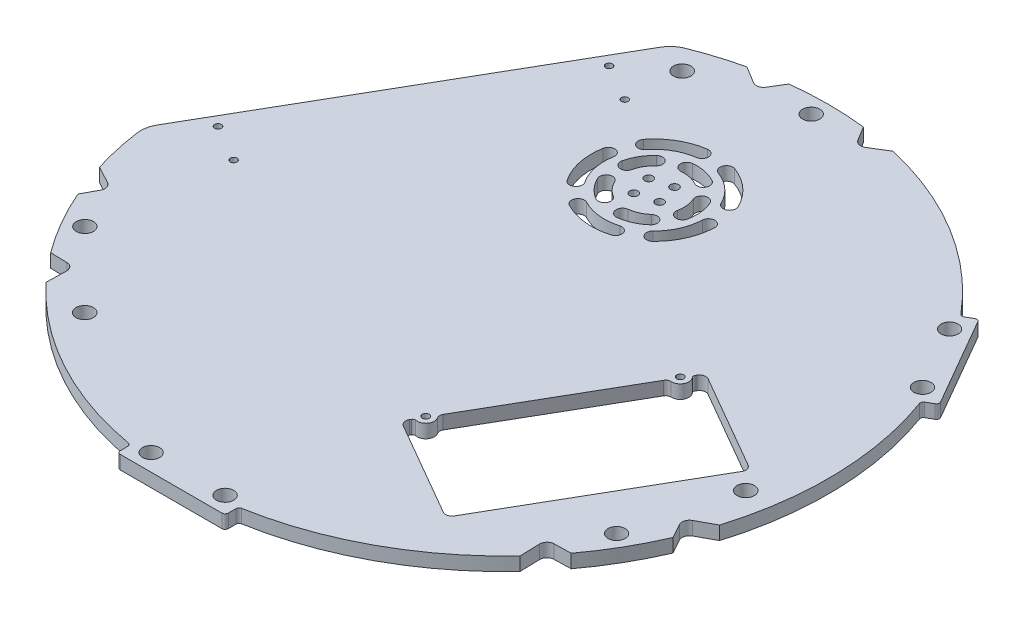
SolidWorks part; units mm, degrees
ref_plane "Front Plane" through (0, 0, 0) normal (0, 0, 1) x (1, 0, 0)
ref_plane "Top Plane" through (0, 0, 0) normal (0, 1, 0) x (1, 0, 0)
ref_plane "Right Plane" through (0, 0, 0) normal (1, 0, 0) x (0, 0, -1)
sketch "Sketch1" plane through (0, 0, 0) normal (0, 1, 0) x (1, 0, 0)
  circle A0 centre (0, 0) radius 152.4
  dimension "D1" = 304.8
extrude "Boss-Extrude1" add sketch "Sketch1" along normal blind 6.35
sketch "Sketch2" plane through (0, 6.35, 0) normal (0, 1, 0) x (1, 0, 0)
  line L0 (0, 144.3376) -> (0, 0) construction
  line L1 (0, 0) -> (0, 144.3376) construction
  line L2 (0, 0) -> (125, -72.1688) construction
  circle A0 centre (0, 144.3376) radius 4.05
  circle A2 centre (125, -72.1688) radius 4.05
  circle A3 centre (-125, -72.1688) radius 4.05
  point P11 (0, 0)
  dimension "D1" = 8.1
  dimension "D2" = 144.3376
  dimension "D4" = 144.3376
  dimension "D5" = 120
  dimension "D3" = 3
extrude "Cut-Extrude1" cut sketch "Sketch2" against normal through all
sketch "Sketch3" plane through (0, 6.35, 0) normal (0, 1, 0) x (1, 0, 0)
  line L0 (0, -150.2684) -> (0, 0) construction
  line L1 (-25.4, -150.2684) -> (25.4, -150.2684)
  line L2 (-25.4, -150.2684) -> (-25.4, -156.6184)
  line L3 (-25.4, -156.6184) -> (25.4, -156.6184)
  line L4 (25.4, -150.2684) -> (25.4, -156.6184)
  dimension "D1" = 50.8
  dimension "D2" = 6.35
extrude "Boss-Extrude2" add sketch "Sketch3" against normal blind 6.35
sketch "Sketch4" plane through (0, 6.35, 0) normal (0, 1, 0) x (1, 0, 0)
  line L2 (-17.4, -148.6184) -> (17.4, -148.6184) construction
  line L3 (0, -148.6184) -> (0, -156.6184) construction
  circle A0 centre (17.4, -148.6184) radius 4.05
  circle A1 centre (-17.4, -148.6184) radius 4.05
extrude "Cut-Extrude2" cut sketch "Sketch4" against normal through all
fillet "Fillet1" radius 1.5 4 edges at (-25.4, 3.175, 150.2684) (-25.4, 3.175, 156.6184) (25.4, 3.175, 150.2684) (25.4, 3.175, 156.6184)
sketch "Sketch5" plane through (0, 0, 0) normal (0, -1, 0) x (1, 0, 0)
  line L0 (-39.9277, -175.6648) -> (-166.1966, 43.0393)
  line L17 (-70.2484, -123.1479) -> (-141.7734, 0.7371) construction
extrude "Cut-Extrude3" cut sketch "Sketch5" against normal through all and the other way through all
sketch "Sketch6" [suppressed] plane through (0, 0, 0) normal (0, -1, 0) x (1, 0, 0)
  line L0 (-173.1347, -15.6374) -> (-100.1097, -142.1204)
  line L1 (-100.1097, -142.1204) -> (-79.3315, -130.1241)
  line L3 (-79.3315, -130.1241) -> (-152.3565, -3.6411)
  line L4 (-152.3565, -3.6411) -> (-173.1347, -15.6374)
  arc A2 (-26.6378, 150.0539) -> (26.6378, 150.0539) centre (0, 0) ccw construction
extrude "Boss-Extrude3" [suppressed] add sketch "Sketch6" against normal blind 6.35
fillet "Fillet2" [suppressed] radius 1.5
sketch "Sketch7" plane through (0, 6.35, 0) normal (0, 1, 0) x (1, 0, 0)
  circle A1 centre (-89.9903, -107.2462) radius 4.1
  circle A3 centre (-47.8828, 131.557) radius 4.1
  circle A5 centre (137.8731, -24.3107) radius 4.1
extrude "Cut-Extrude4" cut sketch "Sketch7" against normal through all
sketch "Sketch8" plane through (0, 0, 0) normal (0, -1, 0) x (1, 0, 0)
  circle A0 centre (-89.9903, 107.2462) radius 15
  circle A1 centre (-89.9903, 107.2462) radius 4.1 construction
  circle A2 centre (-47.8828, -131.557) radius 15
  circle A4 centre (137.8731, 24.3107) radius 15
  circle A5 centre (137.8731, 24.3107) radius 4.1 construction
  dimension "D1" = 30
sketch "Sketch9" plane through (0, 0, 0) normal (0, 1, 0) x (1, 0, 0)
  line L0 (-114.4897, -91.0492) -> (-125.4859, -90.7618)
  line L1 (-111.1769, -94.6245) -> (-111.8439, -120.1454)
  line L3 (0, 0) -> (-125, -72.1688) construction
  line L6 (-136.0957, -53.6264) -> (-141.345, -63.2931)
  line L7 (-137.5356, -48.9698) -> (-159.9709, -36.7869)
  arc A1 (-141.345, -63.2931) -> (-125.4859, -90.7618) centre (-125, -72.1688) ccw
  arc A2 (-159.9709, -36.7869) -> (-111.8439, -120.1454) centre (-125, -72.1688) ccw
  spline S0 degree 3 poles (-114.4897, -91.0492) (-114.0345, -91.0611) (-113.1163, -91.2801) (-111.6342, -92.3884) (-111.1542, -93.7538) (-111.1769, -94.6245) knots 0 0 0 0 0.392699 0.785398 1.570796 1.570796 1.570796 1.570796
  spline S1 degree 3 poles (-136.0957, -53.6264) (-135.8785, -53.2263) (-135.609, -52.3215) (-135.8277, -50.4838) (-136.7702, -49.3854) (-137.5356, -48.9698) knots 0 0 0 0 0.392699 0.785398 1.570796 1.570796 1.570796 1.570796
  dimension "D1" = 49.7477
extrude "Cut-Extrude5" cut sketch "Sketch9" along normal through all
pattern_circular "CirPattern1" count 3 every 120 about axis through (0, 6.35, 0) along (0, -1, 0) of "Cut-Extrude5"
sketch "Sketch10" plane through (0, 6.35, 0) normal (0, 1, 0) x (1, 0, 0)
  line L4 (-19.0051, -114.3124) -> (14.6313, -133.7324)
  line L5 (32.2903, -17.8461) -> (-20.3997, -109.1078)
  line L6 (71.1313, -35.8715) -> (37.4949, -16.4515)
  line L7 (19.8359, -132.3378) -> (72.5259, -41.0761)
  arc A4 (-20.3997, -109.1078) -> (-19.0051, -114.3124) centre (-17.1001, -111.0128) ccw
  arc A5 (37.4949, -16.4515) -> (32.2903, -17.8461) centre (35.5899, -19.7511) ccw
  arc A6 (72.5259, -41.0761) -> (71.1313, -35.8715) centre (69.2263, -39.1711) ccw
  arc A7 (14.6313, -133.7324) -> (19.8359, -132.3378) centre (16.5363, -130.4328) ccw
extrude "Cut-Extrude6" cut sketch "Sketch10" against normal through all
sketch "Sketch12" [suppressed] plane through (0, 0, 0) normal (0, -1, 0) x (1, 0, 0)
  circle A5 centre (-100.754, 34.2057) radius 1.525
  circle A6 centre (-12.004, -119.5138) radius 1.525
  circle A7 centre (70.2684, -72.0138) radius 1.525
  circle A8 centre (-8.599, -16.5116) radius 1.525
  circle A9 centre (-18.4816, 81.7057) radius 1.525
extrude "Cut-Extrude7" [suppressed] cut sketch "Sketch12" against normal blind 25.4
fillet "Fillet4" radius 12.7 2 edges at (-60.6199, 3.175, -139.8248) (-151.4018, 3.175, 17.414)
ref_plane "Plane1" through (0, 0, 0) normal (0.5, 0, -0.866) x (-0.866, 0, -0.5)
mirror "Mirror1" about plane through (0, 0, 0) normal (0.5, 0, -0.866) of "Cut-Extrude2", "Fillet1", "Boss-Extrude2"
sketch "Sketch13" plane through (0, 6.35, 0) normal (0, 1, 0) x (1, 0, 0)
  line L0 (-67.1597, 116.4976) -> (-46.3248, 104.4685) construction
  line L3 (-134.4697, -0.0868) -> (-113.6348, -12.1158) construction
  line L5 (-117.0989, -10.1158) -> (-49.7889, 106.4685) construction
  circle A0 centre (-134.4697, -0.0868) radius 1.6
  circle A1 centre (-117.0989, -10.1158) radius 1.6
  circle A2 centre (-67.1597, 116.4976) radius 1.6
  circle A3 centre (-49.7889, 106.4685) radius 1.6
extrude "Cut-Extrude8" cut sketch "Sketch13" against normal blind 25.4
sketch "Sketch14" [suppressed] plane through (0, 0, 0) normal (0, -1, 0) x (1, 0, 0)
  line L0 (-5.7127, 73.4893) -> (-38.7083, 54.4393) construction
  line L2 (-4.1252, 70.7397) -> (-37.1208, 51.6897)
  line L3 (-7.3002, 76.239) -> (-40.2958, 57.189)
  line L5 (-52.8678, 46.2643) -> (-33.982, 13.5531) construction
  line L6 (-100.0229, 19.0393) -> (-67.0273, 38.0893) construction
  line L7 (-98.4354, 16.2897) -> (-65.4398, 35.3397)
  line L8 (-101.6104, 21.789) -> (-68.6148, 40.839)
  line L9 (3.8123, 56.9915) -> (-29.1833, 37.9415) construction
  line L10 (5.3998, 54.2419) -> (-27.5958, 35.1919)
  line L11 (2.2248, 59.7412) -> (-30.7708, 40.6912)
  line L12 (-90.4979, 2.5415) -> (-57.5023, 21.5915) construction
  line L13 (-88.9104, -0.2081) -> (-55.9148, 18.8419)
  line L14 (-92.0854, 5.2912) -> (-59.0898, 24.3412)
  line L15 (13.3373, 40.4938) -> (-19.6583, 21.4438) construction
  line L16 (14.9248, 37.7441) -> (-18.0708, 18.6941)
  line L17 (11.7498, 43.2434) -> (-21.2458, 24.1934)
  line L18 (-80.9729, -13.9562) -> (-47.9773, 5.0938) construction
  line L19 (-79.3854, -16.7059) -> (-46.3898, 2.3441)
  line L20 (-82.5604, -11.2066) -> (-49.5648, 7.8434)
  line L21 (22.8623, 23.996) -> (-10.1333, 4.946) construction
  line L22 (24.4498, 21.2463) -> (-8.5458, 2.1963)
  line L23 (21.2748, 26.7456) -> (-11.7208, 7.6956)
  line L24 (-71.4479, -30.454) -> (-38.4523, -11.404) construction
  line L25 (-69.8604, -33.2037) -> (-36.8648, -14.1537)
  line L26 (-73.0354, -27.7044) -> (-40.0398, -8.6544)
  line L27 (32.3873, 7.4982) -> (-0.6083, -11.5518) construction
  line L28 (33.9748, 4.7486) -> (0.9792, -14.3014)
  line L29 (30.7998, 10.2478) -> (-2.1958, -8.8022)
  line L30 (-61.9229, -46.9518) -> (-28.9273, -27.9018) construction
  line L31 (-60.3354, -49.7014) -> (-27.3398, -30.6514)
  line L32 (-63.5104, -44.2022) -> (-30.5148, -25.1522)
  line L33 (41.9123, -8.9996) -> (8.9167, -28.0496) construction
  line L34 (43.4998, -11.7492) -> (10.5042, -30.7992)
  line L35 (40.3248, -6.25) -> (7.3292, -25.3)
  line L36 (-52.3979, -63.4496) -> (-19.4023, -44.3996) construction
  line L37 (-50.8104, -66.1992) -> (-17.8148, -47.1492)
  line L38 (-53.9854, -60.7) -> (-20.9898, -41.65)
  line L39 (51.4373, -25.4974) -> (18.4417, -44.5474) construction
  line L40 (53.0248, -28.247) -> (20.0292, -47.297)
  line L41 (49.8498, -22.7477) -> (16.8542, -41.7977)
  line L42 (-42.8729, -79.9474) -> (-9.8773, -60.8974) construction
  line L43 (-41.2854, -82.697) -> (-8.2898, -63.647)
  line L44 (-44.4604, -77.1977) -> (-11.4648, -58.1477)
  line L45 (60.9623, -41.9952) -> (27.9667, -61.0452) construction
  line L46 (62.5498, -44.7448) -> (29.5542, -63.7948)
  line L47 (59.3748, -39.2455) -> (26.3792, -58.2955)
  line L48 (-33.3479, -96.4452) -> (-0.3523, -77.3952) construction
  line L49 (-31.7604, -99.1948) -> (1.2352, -80.1448)
  line L50 (-34.9354, -93.6955) -> (-1.9398, -74.6455)
  line L51 (70.4873, -58.4929) -> (37.4917, -77.5429) construction
  line L52 (72.0748, -61.2426) -> (39.0792, -80.2926)
  line L53 (68.8998, -55.7433) -> (35.9042, -74.7933)
  line L54 (-23.8229, -112.9429) -> (9.1727, -93.8929) construction
  line L55 (-22.2354, -115.6926) -> (10.7602, -96.6426)
  line L56 (-25.4104, -110.1933) -> (7.5852, -91.1433)
  arc A0 (-4.1252, 70.7397) -> (-7.3002, 76.239) centre (-5.7127, 73.4893) ccw
  arc A1 (-40.2958, 57.189) -> (-37.1208, 51.6897) centre (-38.7083, 54.4393) ccw
  arc A2 (-98.4354, 16.2897) -> (-101.6104, 21.789) centre (-100.0229, 19.0393) cw
  arc A3 (-68.6148, 40.839) -> (-65.4398, 35.3397) centre (-67.0273, 38.0893) cw
  arc A4 (5.3998, 54.2419) -> (2.2248, 59.7412) centre (3.8123, 56.9915) ccw
  arc A5 (-30.7708, 40.6912) -> (-27.5958, 35.1919) centre (-29.1833, 37.9415) ccw
  arc A6 (-88.9104, -0.2081) -> (-92.0854, 5.2912) centre (-90.4979, 2.5415) cw
  arc A7 (-59.0898, 24.3412) -> (-55.9148, 18.8419) centre (-57.5023, 21.5915) cw
  arc A8 (14.9248, 37.7441) -> (11.7498, 43.2434) centre (13.3373, 40.4938) ccw
  arc A9 (-21.2458, 24.1934) -> (-18.0708, 18.6941) centre (-19.6583, 21.4438) ccw
  arc A10 (-79.3854, -16.7059) -> (-82.5604, -11.2066) centre (-80.9729, -13.9562) cw
  arc A11 (-49.5648, 7.8434) -> (-46.3898, 2.3441) centre (-47.9773, 5.0938) cw
  arc A12 (24.4498, 21.2463) -> (21.2748, 26.7456) centre (22.8623, 23.996) ccw
  arc A13 (-11.7208, 7.6956) -> (-8.5458, 2.1963) centre (-10.1333, 4.946) ccw
  arc A14 (-69.8604, -33.2037) -> (-73.0354, -27.7044) centre (-71.4479, -30.454) cw
  arc A15 (-40.0398, -8.6544) -> (-36.8648, -14.1537) centre (-38.4523, -11.404) cw
  arc A16 (33.9748, 4.7486) -> (30.7998, 10.2478) centre (32.3873, 7.4982) ccw
  arc A17 (-2.1958, -8.8022) -> (0.9792, -14.3014) centre (-0.6083, -11.5518) ccw
  arc A18 (-60.3354, -49.7014) -> (-63.5104, -44.2022) centre (-61.9229, -46.9518) cw
  arc A19 (-30.5148, -25.1522) -> (-27.3398, -30.6514) centre (-28.9273, -27.9018) cw
  arc A20 (43.4998, -11.7492) -> (40.3248, -6.25) centre (41.9123, -8.9996) ccw
  arc A21 (7.3292, -25.3) -> (10.5042, -30.7992) centre (8.9167, -28.0496) ccw
  arc A22 (-50.8104, -66.1992) -> (-53.9854, -60.7) centre (-52.3979, -63.4496) cw
  arc A23 (-20.9898, -41.65) -> (-17.8148, -47.1492) centre (-19.4023, -44.3996) cw
  arc A24 (53.0248, -28.247) -> (49.8498, -22.7477) centre (51.4373, -25.4974) ccw
  arc A25 (16.8542, -41.7977) -> (20.0292, -47.297) centre (18.4417, -44.5474) ccw
  arc A26 (-41.2854, -82.697) -> (-44.4604, -77.1977) centre (-42.8729, -79.9474) cw
  arc A27 (-11.4648, -58.1477) -> (-8.2898, -63.647) centre (-9.8773, -60.8974) cw
  arc A28 (62.5498, -44.7448) -> (59.3748, -39.2455) centre (60.9623, -41.9952) ccw
  arc A29 (26.3792, -58.2955) -> (29.5542, -63.7948) centre (27.9667, -61.0452) ccw
  arc A30 (-31.7604, -99.1948) -> (-34.9354, -93.6955) centre (-33.3479, -96.4452) cw
  arc A31 (-1.9398, -74.6455) -> (1.2352, -80.1448) centre (-0.3523, -77.3952) cw
  arc A32 (72.0748, -61.2426) -> (68.8998, -55.7433) centre (70.4873, -58.4929) ccw
  arc A33 (35.9042, -74.7933) -> (39.0792, -80.2926) centre (37.4917, -77.5429) ccw
  arc A34 (-22.2354, -115.6926) -> (-25.4104, -110.1933) centre (-23.8229, -112.9429) cw
  arc A35 (7.5852, -91.1433) -> (10.7602, -96.6426) centre (9.1727, -93.8929) cw
  point P5 (-22.2105, 63.9643)
  point P14 (-83.5251, 28.5643)
  point P23 (-12.6855, 47.4665)
  point P30 (-74.0001, 12.0665)
  point P37 (-3.1605, 30.9688)
  point P44 (-64.4751, -4.4312)
  point P51 (6.3645, 14.471)
  point P58 (-54.9501, -20.929)
  point P65 (15.8895, -2.0268)
  point P72 (-45.4251, -37.4268)
  point P79 (25.4145, -18.5246)
  point P86 (-35.9001, -53.9246)
  point P93 (34.9395, -35.0224)
  point P100 (-26.3751, -70.4224)
  point P107 (44.4645, -51.5202)
  point P114 (-16.8501, -86.9202)
  point P121 (53.9895, -68.0179)
  point P128 (-7.3251, -103.4179)
  dimension "D1" = 3.175
extrude "Cut-Extrude9" [suppressed] cut sketch "Sketch14" against normal blind 25.4
sketch "Sketch15" [suppressed] plane through (0, 0, 0) normal (0, -1, 0) x (1, 0, 0)
  line L0 (-163.8426, -16.8717) -> (-117.0989, 10.1158) construction
  line L1 (-117.0989, 10.1158) -> (-113.6348, 12.1158) construction
  line L4 (-133.8294, -77.2664) -> (-91.8195, -53.012) construction
  circle A0 centre (-163.8426, -16.8717) radius 1.6
  circle A1 centre (-117.0989, 10.1158) radius 1.6
  circle A2 centre (-49.7889, -106.4685) radius 1.6
  circle A3 centre (-96.5326, -133.456) radius 1.6
  dimension "D1" = 3.2
  dimension "D2" = 4
  dimension "D3" = 53.975
extrude "Cut-Extrude10" [suppressed] cut sketch "Sketch15" against normal blind 25.4
sketch "Sketch16" [suppressed] plane through (0, 0, 0) normal (0, -1, 0) x (1, 0, 0)
  line L3 (14.4941, 68.99) -> (6.784, 64.5385) construction
  circle A0 centre (-14.1903, 101.2728) radius 1.6
  circle A1 centre (28.1097, 28.0071) radius 1.6
extrude "Cut-Extrude11" [suppressed] cut sketch "Sketch16" against normal blind 25.4
sketch "Sketch17" plane through (0, 78.2, 0) normal (0, 1, 0) x (1, 0, 0)
  arc A20 (15.1344, 86.829) -> (20.521, 89.4719) centre (17.8277, 88.1505) ccw
  arc A21 (20.521, 89.4719) -> (4.1921, 104.1745) centre (-5.9629, 76.4775) ccw
  arc A22 (15.1344, 86.829) -> (2.1267, 98.5412) centre (-5.9629, 76.4775) ccw
  arc A23 (4.1921, 104.1745) -> (2.1267, 98.5412) centre (3.1594, 101.3579) ccw
  arc A24 (-9.2883, 99.741) -> (-10.1374, 105.6806) centre (-9.7129, 102.7108) ccw
  arc A25 (-9.2883, 99.741) -> (-24.4469, 90.9892) centre (-5.9629, 76.4775) ccw
  arc A26 (-10.1374, 105.6806) -> (-29.1663, 94.6943) centre (-5.9629, 76.4775) ccw
  arc A27 (-29.1663, 94.6943) -> (-24.4469, 90.9892) centre (-26.8066, 92.8417) ccw
  arc A28 (10.4015, 59.6115) -> (14.5796, 55.3054) centre (12.4905, 57.4585) ccw
  arc A29 (14.5796, 55.3054) -> (23.5167, 75.3784) centre (-5.9629, 76.4775) ccw
  arc A30 (10.4015, 59.6115) -> (17.5208, 75.6019) centre (-5.9629, 76.4775) ccw
  arc A31 (23.5167, 75.3784) -> (17.5208, 75.6019) centre (20.5187, 75.4901) ccw
  circle A32 centre (-12.025, 79.9775) radius 1.95
  circle A33 centre (-2.4629, 82.5396) radius 1.95
  circle A34 centre (0.0993, 72.9775) radius 1.95
  circle A35 centre (-9.4629, 70.4153) radius 1.95
  arc A36 (-15.4649, 86.759) -> (-19.618, 79.5657) centre (-5.9629, 76.4775) ccw
  arc A37 (-15.4649, 86.759) -> (-19.5372, 91.1654) centre (-17.5011, 88.9622) ccw
  arc A38 (-19.5372, 91.1654) -> (-25.4702, 80.8892) centre (-5.9629, 76.4775) ccw
  arc A39 (-25.4702, 80.8892) -> (-19.618, 79.5657) centre (-22.5441, 80.2275) ccw
  arc A40 (0.8792, 88.6916) -> (3.8115, 93.9263) centre (2.3454, 91.309) ccw
  arc A41 (0.8792, 88.6916) -> (-7.2454, 90.4186) centre (-5.9629, 76.4775) ccw
  arc A42 (-7.7951, 96.3934) -> (-7.2454, 90.4186) centre (-7.5203, 93.406) ccw
  arc A43 (3.8115, 93.9263) -> (-7.7951, 96.3934) centre (-5.9629, 76.4775) ccw
  arc A44 (7.7678, 73.7447) -> (13.6524, 72.5735) centre (10.7101, 73.1591) ccw
  arc A45 (7.7678, 73.7447) -> (6.8996, 82.0053) centre (-5.9629, 76.4775) ccw
  arc A46 (12.4121, 84.3744) -> (6.8996, 82.0053) centre (9.6558, 83.1899) ccw
  arc A47 (13.6524, 72.5735) -> (12.4121, 84.3744) centre (-5.9629, 76.4775) ccw
  arc A48 (-4.3189, 62.5743) -> (-3.6143, 56.6158) centre (-3.9666, 59.5951) ccw
  arc A49 (-4.3189, 62.5743) -> (3.2692, 65.9527) centre (-5.9629, 76.4775) ccw
  arc A50 (7.2257, 61.4421) -> (3.2692, 65.9527) centre (5.2475, 63.6974) ccw
  arc A51 (-3.6143, 56.6158) -> (7.2257, 61.4421) centre (-5.9629, 76.4775) ccw
  arc A52 (-18.6775, 70.6177) -> (-24.1267, 68.1063) centre (-21.4021, 69.362) ccw
  arc A53 (-18.6775, 70.6177) -> (-13.1196, 64.445) centre (-5.9629, 76.4775) ccw
  arc A54 (-16.1868, 59.2882) -> (-13.1196, 64.445) centre (-14.6532, 61.8666) ccw
  arc A55 (-24.1267, 68.1063) -> (-16.1868, 59.2882) centre (-5.9629, 76.4775) ccw
  arc A56 (-16.9464, 55.7022) -> (-19.7508, 50.3979) centre (-18.3486, 53.0501) ccw
  arc A57 (-19.7508, 50.3979) -> (2.1015, 48.1011) centre (-5.9629, 76.4775) ccw
  arc A58 (-16.9464, 55.7022) -> (0.4613, 53.8726) centre (-5.9629, 76.4775) ccw
  arc A59 (2.1015, 48.1011) -> (0.4613, 53.8726) centre (1.2814, 50.9869) ccw
  arc A60 (-29.1154, 80.5036) -> (-35.0267, 81.5315) centre (-32.071, 81.0175) ccw
  arc A61 (-35.0267, 81.5315) -> (-30.4583, 60.039) centre (-5.9629, 76.4775) ccw
  arc A62 (-29.1154, 80.5036) -> (-25.4762, 63.3824) centre (-5.9629, 76.4775) ccw
  arc A63 (-30.4583, 60.039) -> (-25.4762, 63.3824) centre (-27.9673, 61.7107) ccw
  point P63 (-5.9629, 76.4775)
  point P76 (-5.9629, 76.4775)
  dimension "D1" = 5
  dimension "D2" = 5
extrude "Cut-Extrude12" cut sketch "Sketch17" against normal through all
sketch "Sketch18" plane through (0, 6.35, 0) normal (0, 1, 0) x (1, 0, 0)
  line L0 (-20.2848, -98.9089) -> (23.5152, -23.045) construction
  line L1 (1.6152, -60.977) -> (5.9453, -63.477) construction
  line L2 (32.2903, -17.8461) -> (-20.3997, -109.1078) construction
  line L3 (-19.0051, -114.3124) -> (14.6313, -133.7324) construction
  circle A0 centre (-20.2848, -98.9089) radius 1.6
  circle A1 centre (23.5152, -23.045) radius 1.6
  dimension "D2" = 12.7
  dimension "D3" = 3.2
  dimension "D1" = 5
extrude "Cut-Extrude13" cut sketch "Sketch18" against normal through all
sketch "Sketch19" plane through (0, 6.35, 0) normal (0, 1, 0) x (1, 0, 0)
  line L0 (25.8653, -131.4195) -> (28.4053, -127.0201) construction
  line L1 (24.4905, -130.6258) -> (27.0305, -126.2264)
  line L2 (27.2401, -132.2133) -> (29.7801, -127.8139)
  line L3 (30.8146, -134.277) -> (33.3546, -129.8776) construction
  line L4 (29.4398, -133.4833) -> (31.9798, -129.0839)
  line L5 (32.1895, -135.0708) -> (34.7295, -130.6714)
  line L6 (19.8359, -132.3378) -> (72.5259, -41.0761) construction
  line L7 (-19.0051, -114.3124) -> (14.6313, -133.7324) construction
  line L8 (30.8146, -134.277) -> (25.8653, -131.4195) construction
  line L9 (42.2446, -114.4797) -> (37.2953, -111.6222) construction
  line L10 (37.2953, -111.6222) -> (39.8353, -107.2228) construction
  line L11 (35.9205, -110.8284) -> (38.4605, -106.429)
  line L12 (38.6701, -112.4159) -> (41.2101, -108.0165)
  line L13 (42.2446, -114.4797) -> (44.7846, -110.0803) construction
  line L14 (40.8698, -113.6859) -> (43.4098, -109.2865)
  line L15 (43.6195, -115.2734) -> (46.1595, -110.874)
  line L16 (53.6746, -94.6824) -> (48.7253, -91.8249) construction
  line L17 (48.7253, -91.8249) -> (51.2653, -87.4254) construction
  line L18 (47.3505, -91.0311) -> (49.8905, -86.6317)
  line L19 (50.1001, -92.6186) -> (52.6401, -88.2192)
  line L20 (53.6746, -94.6824) -> (56.2146, -90.2829) construction
  line L21 (52.2998, -93.8886) -> (54.8398, -89.4892)
  line L22 (55.0495, -95.4761) -> (57.5895, -91.0767)
  line L23 (65.1046, -74.885) -> (60.1553, -72.0275) construction
  line L24 (60.1553, -72.0275) -> (62.6953, -67.6281) construction
  line L25 (58.7805, -71.2338) -> (61.3205, -66.8344)
  line L26 (61.5301, -72.8213) -> (64.0701, -68.4219)
  line L27 (65.1046, -74.885) -> (67.6446, -70.4856) construction
  line L28 (63.7298, -74.0913) -> (66.2698, -69.6919)
  line L29 (66.4795, -75.6788) -> (69.0195, -71.2794)
  line L30 (76.5346, -55.0877) -> (71.5853, -52.2302) construction
  line L31 (71.5853, -52.2302) -> (74.1253, -47.8308) construction
  line L32 (70.2105, -51.4364) -> (72.7505, -47.037)
  line L33 (72.9601, -53.0239) -> (75.5001, -48.6245)
  line L34 (76.5346, -55.0877) -> (79.0746, -50.6883) construction
  line L35 (75.1598, -54.2939) -> (77.6998, -49.8945)
  line L36 (77.9095, -55.8814) -> (80.4495, -51.482)
  arc A0 (24.4905, -130.6258) -> (27.2401, -132.2133) centre (25.8653, -131.4195) ccw
  arc A1 (29.7801, -127.8139) -> (27.0305, -126.2264) centre (28.4053, -127.0201) ccw
  arc A2 (29.4398, -133.4833) -> (32.1895, -135.0708) centre (30.8146, -134.277) ccw
  arc A3 (34.7295, -130.6714) -> (31.9798, -129.0839) centre (33.3546, -129.8776) ccw
  arc A4 (35.9205, -110.8284) -> (38.6701, -112.4159) centre (37.2953, -111.6222) ccw
  arc A5 (41.2101, -108.0165) -> (38.4605, -106.429) centre (39.8353, -107.2228) ccw
  arc A6 (40.8698, -113.6859) -> (43.6195, -115.2734) centre (42.2446, -114.4797) ccw
  arc A7 (46.1595, -110.874) -> (43.4098, -109.2865) centre (44.7846, -110.0803) ccw
  arc A8 (47.3505, -91.0311) -> (50.1001, -92.6186) centre (48.7253, -91.8249) ccw
  arc A9 (52.6401, -88.2192) -> (49.8905, -86.6317) centre (51.2653, -87.4254) ccw
  arc A10 (52.2998, -93.8886) -> (55.0495, -95.4761) centre (53.6746, -94.6824) ccw
  arc A11 (57.5895, -91.0767) -> (54.8398, -89.4892) centre (56.2146, -90.2829) ccw
  arc A12 (58.7805, -71.2338) -> (61.5301, -72.8213) centre (60.1553, -72.0275) ccw
  arc A13 (64.0701, -68.4219) -> (61.3205, -66.8344) centre (62.6953, -67.6281) ccw
  arc A14 (63.7298, -74.0913) -> (66.4795, -75.6788) centre (65.1046, -74.885) ccw
  arc A15 (69.0195, -71.2794) -> (66.2698, -69.6919) centre (67.6446, -70.4856) ccw
  arc A16 (70.2105, -51.4364) -> (72.9601, -53.0239) centre (71.5853, -52.2302) ccw
  arc A17 (75.5001, -48.6245) -> (72.7505, -47.037) centre (74.1253, -47.8308) ccw
  arc A18 (75.1598, -54.2939) -> (77.9095, -55.8814) centre (76.5346, -55.0877) ccw
  arc A19 (80.4495, -51.482) -> (77.6998, -49.8945) centre (79.0746, -50.6883) ccw
  point P2 (27.1353, -129.2198)
  point P7 (32.0846, -132.0773)
  point P24 (38.5653, -109.4225)
  point P29 (43.5146, -112.28)
  point P40 (49.9953, -89.6251)
  point P45 (54.9446, -92.4826)
  point P56 (61.4253, -69.8278)
  point P61 (66.3746, -72.6853)
  point P72 (72.8553, -50.0305)
  point P77 (77.8046, -52.888)
  dimension "D5" = 7.62
  dimension "D1" = 2.54
  dimension "D2" = 3.175
  dimension "D3" = 5.08
  dimension "D4" = 3.175
extrude "Cut-Extrude14" cut sketch "Sketch19" against normal through all
sketch "Sketch20" [suppressed] plane through (0, 0, 0) normal (0, -1, 0) x (1, 0, 0)
  point P0 (0, 0)
sketch "Sketch21" plane through (0, 0, 0) normal (0, -1, 0) x (1, 0, 0)
  line L0 (-28.0204, 109.1074) -> (28.4796, 11.2465)
  line L1 (-28.0204, 109.1074) -> (28.3795, 141.6699)
  line L2 (28.4796, 11.2465) -> (84.8795, 43.809)
  line L3 (28.3795, 141.6699) -> (84.8795, 43.809)
  line L4 (32.2903, 17.8461) -> (-20.3997, 109.1078) construction
  line L5 (-19.0051, 114.3124) -> (14.6313, 133.7324) construction
  line L6 (71.1313, 35.8715) -> (37.4949, 16.4515) construction
  line L7 (32.1895, 135.0708) -> (34.7295, 130.6714) construction
  circle A0 centre (-20.2848, 98.9089) radius 1.6 construction
extrude "Boss-Extrude4" add sketch "Sketch21" against normal up to surface (6.35 mm away) up to face at (77.8046, 6.35, 52.888)
sketch "Sketch22" plane through (0, 6.35, 0) normal (0, 1, 0) x (1, 0, 0)
  line L0 (31.0644, -78.4991) -> (75.6088, -104.2168)
  line L1 (29.9663, -74.401) -> (30.2811, -73.8556)
  line L2 (79.7069, -103.1187) -> (129.1569, -17.4688)
  line L3 (83.5144, 12.347) -> (128.0588, -13.3708)
  line L8 (79.1014, 10.7036) -> (79.4163, 11.2489)
  line L9 (35.7194, -64.4362) -> (73.6631, 1.2842)
  arc A0 (75.6088, -104.2168) -> (79.7069, -103.1187) centre (77.1088, -101.6187) ccw
  arc A1 (29.9663, -74.401) -> (31.0644, -78.4991) centre (32.5644, -75.901) ccw
  arc A2 (79.4163, 11.2489) -> (83.5144, 12.347) centre (82.0144, 9.7489) cw
  arc A3 (129.1569, -17.4688) -> (128.0588, -13.3708) centre (126.5588, -15.9688) ccw
  arc A7 (75.9903, 2.551) -> (79.2426, 9.2356) centre (76.1929, 6.5859) ccw
  arc A8 (73.6631, 1.2842) -> (75.9903, 2.551) centre (75.8628, 0.0142) cw
  arc A10 (31.623, -73.2439) -> (35.7859, -67.085) centre (32.3929, -69.2779) ccw
  arc A11 (35.7194, -64.4362) -> (35.7859, -67.085) centre (37.9191, -65.7062) ccw
  arc A12 (30.2811, -73.8556) -> (31.623, -73.2439) centre (31.381, -74.4906) cw
  arc A13 (79.1014, 10.7036) -> (79.2426, 9.2356) centre (80.2013, 10.0686) ccw
  circle A14 centre (32.3929, -69.2779) radius 1.651
  circle A15 centre (76.1929, 6.5859) radius 1.651
  dimension "D5" = 3
  dimension "D8" = 2.54
  dimension "D9" = 1.27
  dimension "D10" = 3.302
extrude "Cut-Extrude15" cut sketch "Sketch22" against normal blind 6.35
sketch "Sketch23" [suppressed] plane through (0, 0, 0) normal (0, -1, 0) x (1, 0, 0)
  circle A0 centre (38.4874, 71.6419) radius 1.5 construction
  circle A1 centre (81.2874, -2.4899) radius 1.5 construction
  circle A2 centre (38.4874, 71.6419) radius 1.5
  circle A3 centre (81.2874, -2.4899) radius 1.5
extrude "Cut-Extrude16" [suppressed] cut sketch "Sketch23" against normal through all
